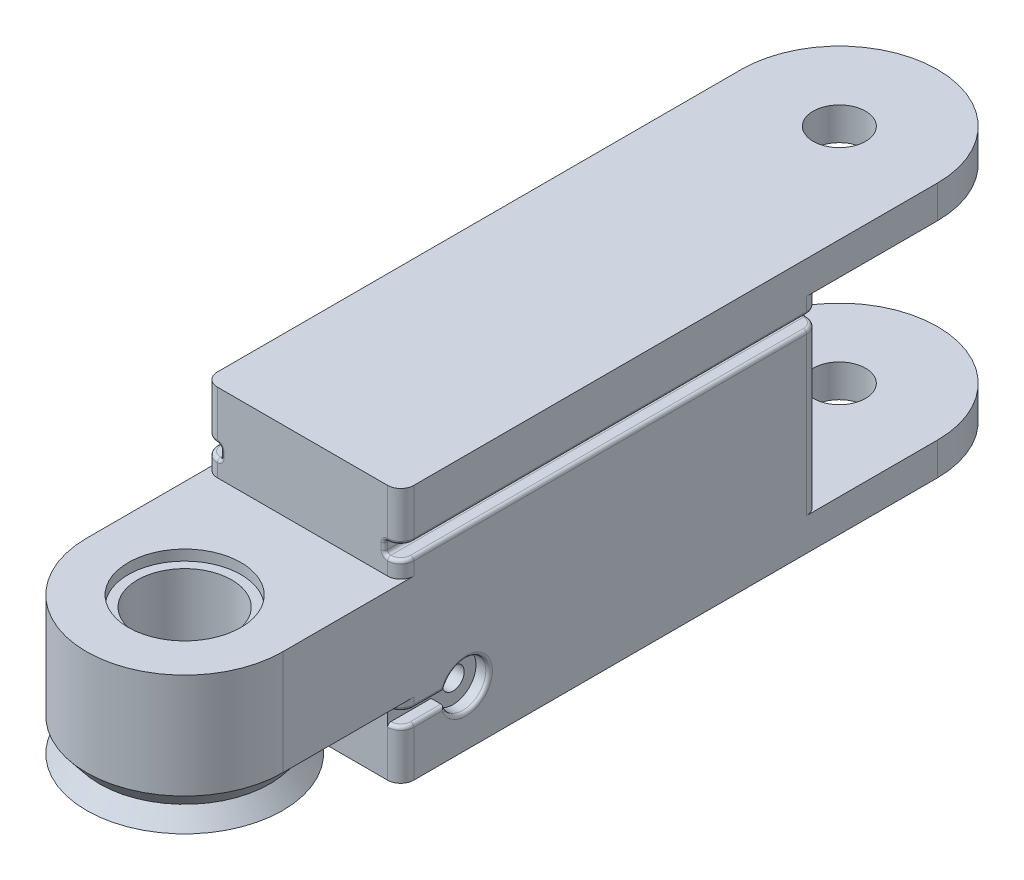
SolidWorks part; units mm, degrees
ref_plane "정면" through (0, 0, 0) normal (0, 0, 1) x (1, 0, 0)
ref_plane "윗면" through (0, 0, 0) normal (0, 1, 0) x (1, 0, 0)
ref_plane "우측면" through (0, 0, 0) normal (1, 0, 0) x (0, 0, -1)
sketch "스케치1" plane through (0, 0, 0) normal (0, 1, 0) x (1, 0, 0)
  line L0 (0, 0) -> (0, 50) construction
  line L1 (-7.5, 0) -> (-7.5, 50)
  line L2 (7.5, 0) -> (7.5, 50)
  arc A0 (-7.5, 0) -> (7.5, 0) centre (0, 0) ccw
  arc A1 (7.5, 50) -> (-7.5, 50) centre (0, 50) ccw
  point P3 (0, 25)
  dimension "D1" = 7.5
  dimension "D2" = 50
extrude "보스-돌출1" add sketch "스케치1" along normal blind 8
sketch "스케치2" plane through (0, 0, 0) normal (0, 0, 1) x (1, 0, 0)
  line L0 (0, 0) -> (0, -2.5)
  line L1 (0, -4.4) -> (0, 4.4) construction
  line L2 (0, -2.5) -> (-7.5, -2.5)
  line L3 (-7.5, -2.5) -> (-6.5, -1.25)
  line L4 (-6.5, -1.25) -> (-7.5, 0)
  line L5 (8.25, 0) -> (-8.25, 0) construction
  line L6 (-7.5, 0) -> (0, 0)
  line L7 (-7.5, 8) -> (-7.5, 0) construction
  line L8 (0, 0) -> (0, -2.5) construction
  point P16 (0, -1.25)
  dimension "D1" = 2.5
  dimension "D2" = 6.5
revolve "회전1" add sketch "스케치2" angle 360 about L8
sketch "스케치3" plane through (0, 0, 0) normal (0, -1, 0) x (1, 0, 0)
  line L0 (7.5, -50) -> (7.5, -9)
  line L2 (-7.5, -9) -> (-7.5, -50)
  line L3 (-7.5, -9) -> (7.5, -9)
  arc A0 (-7.5, -50) -> (7.5, -50) centre (0, -50) ccw
  arc A1 (-7.5, -50) -> (7.5, -50) centre (0, -50) ccw construction
extrude "보스-돌출2" add sketch "스케치3" along normal blind 5.5 and the other way offset from surface (14 mm away) 6 other way up to face at (0, 8, -25)
sketch "스케치4" plane through (0, 0, 0) normal (0, 1, 0) x (1, 0, 0)
  line L0 (7.5, 50) -> (7.5, 9) construction
  line L2 (-7.5, 50) -> (-7.5, 41)
  line L3 (-7.5, 41) -> (7.5, 41)
  line L4 (7.5, 50) -> (7.5, 41)
  arc A0 (7.5, 50) -> (-7.5, 50) centre (0, 50) ccw
  arc A1 (7.5, 50) -> (-7.5, 50) centre (0, 50) ccw construction
  dimension "D1" = 9
extrude "컷-돌출1" cut sketch "스케치4" against normal offset from surface 2.5 and the other way offset from surface (11.5 mm away) 2.5 up to face at (0, -5.5, -31.375) other way up to face at (0, 14, -31.375)
fillet "필렛1" radius 1 6 edges at (7.5, 4.25, -41) (-7.5, 4.25, -41) (7.5, 11, -9) (7.5, -2.75, -9) (-7.5, -2.75, -9) (-7.5, 11, -9)
sketch "스케치5" plane through (0, 0, -9) normal (0, 0, 1) x (1, 0, 0)
  line L0 (-7.5, -5.5) -> (-7.5, 0) construction
  line L1 (-7.5, -0.75) -> (-6.5, -0.75)
  line L2 (-7.5, -0.75) -> (-7.5, -1.75)
  line L3 (-7.5, -1.75) -> (-6.5, -1.75)
  line L4 (-6.5, -0.75) -> (-6.5, -1.75)
  line L5 (7.5, 0) -> (7.5, -5.5) construction
  line L6 (7.5, -0.75) -> (6.5, -0.75)
  line L7 (7.5, -0.75) -> (7.5, -1.75)
  line L8 (7.5, -1.75) -> (6.5, -1.75)
  line L9 (6.5, -0.75) -> (6.5, -1.75)
  line L10 (6.5, -1.25) -> (-6.5, -1.25) construction
  point P14 (-7.5, -1.25)
  point P15 (7.5, -1.25)
  dimension "D1" = 1
  dimension "D2" = 1
  dimension "D3" = 1
  dimension "D4" = 1
extrude "컷-돌출2" cut sketch "스케치5" against normal blind 5
sketch "스케치6" plane through (7.5, 0, 0) normal (1, 0, 0) x (0, 0, -1)
  line L0 (14, -0.75) -> (9, -0.75) construction
  line L1 (14, -1.75) -> (10, -1.75) construction
  line L2 (14, -0.75) -> (14, -1.75) construction
  circle A0 centre (14, -1.25) radius 0.5
extrude "컷-돌출3" cut sketch "스케치6" against normal up to surface (15 mm away) up to face at (-7.5, 2.8125, -23)
sketch "스케치7" plane through (7.5, 0, 0) normal (1, 0, 0) x (0, 0, -1)
  circle A0 centre (14, -1.25) radius 1.75
  dimension "D1" = 3.5
extrude "컷-돌출4" cut sketch "스케치7" against normal up to surface (1 mm away) up to face at (6.5, -1.25, -11.375)
sketch "스케치8" plane through (-7.5, 0, 0) normal (-1, 0, 0) x (0, 0, 1)
  circle A0 centre (-14, -1.25) radius 1.75
  dimension "D1" = 3.5
extrude "컷-돌출5" cut sketch "스케치8" against normal up to surface (1 mm away) up to face at (-6.5, -1.25, -11.375)
sketch "스케치9" plane through (0, 0, -9) normal (0, 0, 1) x (1, 0, 0)
  line L0 (7.5, 14) -> (7.5, 8) construction
  line L1 (7.5, 10.25) -> (6.25, 10.25)
  line L2 (7.5, 10.25) -> (7.5, 9.25)
  line L3 (7.5, 9.25) -> (6.25, 9.25)
  line L4 (6.25, 10.25) -> (6.25, 9.25)
  line L5 (-7.5, 8) -> (-7.5, 14) construction
  line L6 (-7.5, 10.25) -> (-6.25, 10.25)
  line L7 (-7.5, 10.25) -> (-7.5, 9.25)
  line L8 (-7.5, 9.25) -> (-6.25, 9.25)
  line L9 (-6.25, 10.25) -> (-6.25, 9.25)
  line L10 (-6.5, 8) -> (6.5, 8) construction
  dimension "D1" = 1
  dimension "D2" = 1
  dimension "D3" = 1.25
  dimension "D4" = 1.25
  dimension "D5" = 1.25
extrude "컷-돌출6" cut sketch "스케치9" against normal up to surface (32 mm away) up to face at (0, 4.25, -41)
fillet "필렛2" radius 0.25 30 edges at (7.2071, 9.25, -40.7071) (7.2071, 9.25, -9.2929) (7.2071, 10.25, -40.7071) (7.2071, 10.25, -9.2929) (7.2071, -1.75, -9.2929) (7.2071, -0.75, -9.2929) (-7.2071, 10.25, -40.7071) (-7.2071, 10.25, -9.2929) (-7.2071, 9.25, -40.7071) (-7.2071, 9.25, -9.2929) (-7.2071, -1.75, -9.2929) (-7.2071, -0.75, -9.2929) (7.5, 9.25, -25) (7.5, 10.25, -25) (7.5, -1.25, -15.75) (7.5, -1.75, -11.1615) (7.5, -0.75, -11.1615) (-7.5, 10.25, -25) (-7.5, 9.25, -25) (-7.5, -1.25, -15.75) (-7.5, -1.75, -11.1615) (-7.5, -0.75, -11.1615) (6.25, 9.75, -41) (6.25, 9.75, -9) (-6.25, 9.75, -41) (-6.25, 9.75, -9) (-6.25, 9.25, -25) (6.25, 10.25, -25) (6.25, 9.25, -25) (-6.25, 10.25, -25)
sketch "스케치10" plane through (0, -2.5, 0) normal (0, -1, 0) x (1, 0, 0)
  circle A0 centre (0, 0) radius 2
  dimension "D1" = 4
extrude "컷-돌출7" cut sketch "스케치10" against normal up to surface (10.5 mm away) contours A0 up to face at (0, 8, -5.0143)
sketch "스케치11" plane through (0, 14, 0) normal (0, 1, 0) x (1, 0, 0)
  circle A0 centre (0, 50) radius 2
  arc A1 (7.5, 50) -> (-7.5, 50) centre (0, 50) ccw construction
  dimension "D1" = 4
extrude "컷-돌출8" cut sketch "스케치11" against normal up to surface (19.5 mm away) up to face at (0, -5.5, -24.181)
sketch "스케치12" plane through (0, -2.5, 0) normal (0, -1, 0) x (1, 0, 0)
  circle A0 centre (0, 0) radius 3.6
  circle A1 centre (0, 0) radius 2 construction
  dimension "D1" = 7.2
extrude "컷-돌출9" cut sketch "스케치12" against normal up to surface (10.5 mm away) up to face at (0, 8, 2)
sketch "스케치13" plane through (0, -2.5, 0) normal (0, -1, 0) x (1, 0, 0)
  circle A0 centre (0, 0) radius 4.3
  dimension "D1" = 8.6
sketch "스케치14" plane through (0, 8, 0) normal (0, 1, 0) x (1, 0, 0)
  circle A0 centre (0, 0) radius 4.3
  dimension "D1" = 8.6
extrude "컷-돌출10" cut sketch "스케치13" against normal blind 0.8
extrude "컷-돌출11" cut sketch "스케치14" against normal blind 0.8
sketch "스케치15" plane through (-6.5, 0, 0) normal (-1, 0, 0) x (0, 0, 1)
  circle A0 centre (-14, -1.25) radius 0.85
  dimension "D1" = 1.7
extrude "컷-돌출12" cut sketch "스케치15" against normal up to surface (13 mm away) up to face at (6.5, -1.25, -10.7449)
